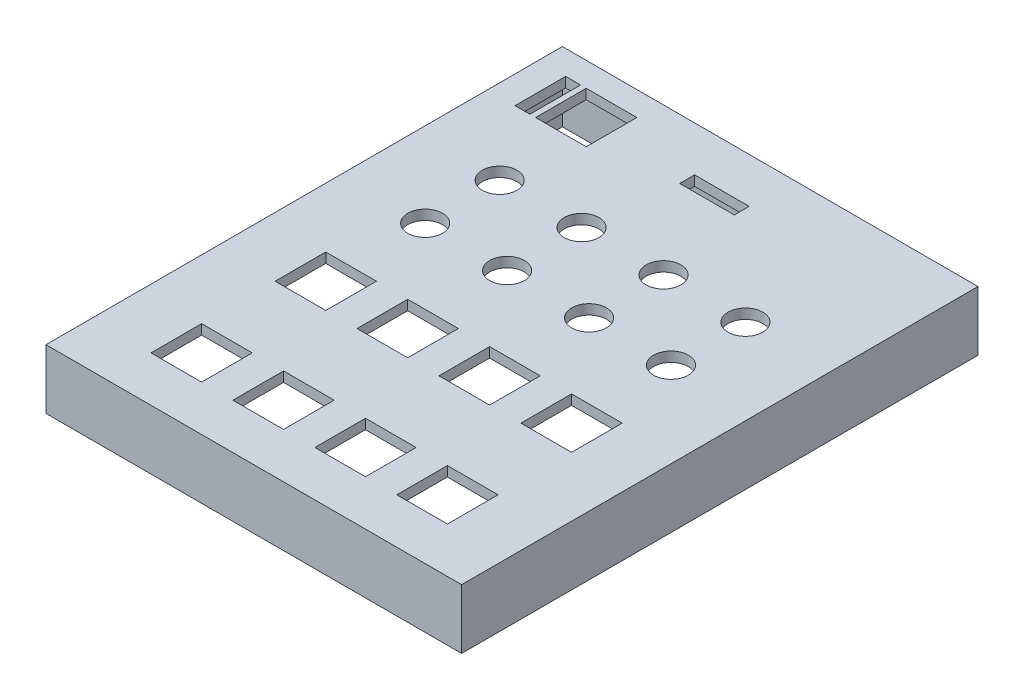
SolidWorks part; units mm, degrees
note: The reader was unsure of these and kept them because the rebuilt part matched: shared geometry of "Sketch1<3>".
ref_plane "Front Plane" through (0, 0, 0) normal (0, 0, 1) x (1, 0, 0)
ref_plane "Top Plane" through (0, 0, 0) normal (0, 1, 0) x (1, 0, 0)
ref_plane "Right Plane" through (0, 0, 0) normal (1, 0, 0) x (0, 0, -1)
sketch "Sketch1" plane through (0, 0, 0) normal (0, 1, 0) x (1, 0, 0)
  line L0 (-91.3497, -4.9786) -> (-81.1497, -4.9786)
  line L1 (-117.8497, 77.6786) -> (-38.1497, 77.6786)
  line L2 (-117.8497, 77.6786) -> (-117.8497, -22.3214)
  line L3 (-117.8497, -22.3214) -> (-38.1497, -22.3214)
  line L4 (-38.1497, 77.6786) -> (-38.1497, -22.3214)
  line L5 (-107.8497, -4.9786) -> (-97.6497, -4.9786)
  line L6 (-107.8497, -4.9786) -> (-107.8497, -15.1786)
  line L7 (-107.8497, -15.1786) -> (-97.6497, -15.1786)
  line L8 (-97.6497, -4.9786) -> (-97.6497, -15.1786)
  line L9 (-81.1497, -4.9786) -> (-81.1497, -15.1786)
  line L10 (-91.3497, -15.1786) -> (-81.1497, -15.1786)
  line L11 (-91.3497, -4.9786) -> (-91.3497, -15.1786)
  line L12 (-74.8497, -4.9786) -> (-64.6497, -4.9786)
  line L13 (-64.6497, -4.9786) -> (-64.6497, -15.1786)
  line L14 (-74.8497, -15.1786) -> (-64.6497, -15.1786)
  line L15 (-74.8497, -4.9786) -> (-74.8497, -15.1786)
  line L16 (-58.3497, -4.9786) -> (-48.1497, -4.9786)
  line L17 (-48.1497, -4.9786) -> (-48.1497, -15.1786)
  line L18 (-58.3497, -15.1786) -> (-48.1497, -15.1786)
  line L19 (-58.3497, -4.9786) -> (-58.3497, -15.1786)
  line L20 (-91.3497, 20.0214) -> (-81.1497, 20.0214)
  line L21 (-107.8497, 20.0214) -> (-97.6497, 20.0214)
  line L22 (-107.8497, 20.0214) -> (-107.8497, 9.8214)
  line L23 (-107.8497, 9.8214) -> (-97.6497, 9.8214)
  line L24 (-97.6497, 20.0214) -> (-97.6497, 9.8214)
  line L25 (-81.1497, 20.0214) -> (-81.1497, 9.8214)
  line L26 (-91.3497, 9.8214) -> (-81.1497, 9.8214)
  line L27 (-91.3497, 20.0214) -> (-91.3497, 9.8214)
  line L28 (-74.8497, 20.0214) -> (-64.6497, 20.0214)
  line L29 (-64.6497, 20.0214) -> (-64.6497, 9.8214)
  line L30 (-74.8497, 9.8214) -> (-64.6497, 9.8214)
  line L31 (-74.8497, 20.0214) -> (-74.8497, 9.8214)
  line L32 (-58.3497, 20.0214) -> (-48.1497, 20.0214)
  line L33 (-48.1497, 20.0214) -> (-48.1497, 9.8214)
  line L34 (-58.3497, 9.8214) -> (-48.1497, 9.8214)
  line L35 (-58.3497, 20.0214) -> (-58.3497, 9.8214)
  line L36 (-119.8497, 79.6786) -> (-119.8497, -24.3214)
  line L37 (-84.1579, 67.6152) -> (-73.1579, 67.6152)
  line L38 (-84.1579, 67.6152) -> (-84.1579, 70.6152)
  line L39 (-84.1579, 70.6152) -> (-73.1579, 70.6152)
  line L40 (-73.1579, 67.6152) -> (-73.1579, 70.6152)
  line L41 (-84.1579, 67.6152) -> (-73.1579, 70.6152) construction
  line L42 (-84.1579, 70.6152) -> (-73.1579, 67.6152) construction
  line L43 (-114.3174, 74.8023) -> (-111.3174, 74.8023)
  line L44 (-114.3174, 74.8023) -> (-114.3174, 64.6023)
  line L45 (-114.3174, 64.6023) -> (-111.3174, 64.6023)
  line L46 (-111.3174, 74.8023) -> (-111.3174, 64.6023)
  line L47 (-114.3174, 74.8023) -> (-111.3174, 64.6023) construction
  line L48 (-114.3174, 64.6023) -> (-111.3174, 74.8023) construction
  line L49 (-110.173, 74.8023) -> (-99.973, 74.8023)
  line L50 (-110.173, 74.8023) -> (-110.173, 64.6023)
  line L51 (-110.173, 64.6023) -> (-99.973, 64.6023)
  line L52 (-99.973, 74.8023) -> (-99.973, 64.6023)
  line L53 (-119.8497, -24.3214) -> (-36.1497, -24.3214)
  line L54 (-36.1497, 79.6786) -> (-36.1497, -24.3214)
  line L55 (-119.8497, 79.6786) -> (-36.1497, 79.6786)
  circle A0 centre (-102.8497, 35.0426) radius 3.5
  circle A1 centre (-86.3497, 35.0426) radius 3.5
  circle A2 centre (-69.8497, 35.0426) radius 3.5
  circle A3 centre (-53.3497, 35.0426) radius 3.5
  circle A4 centre (-102.8497, 50.0426) radius 3.5
  circle A5 centre (-86.3497, 50.0426) radius 3.5
  circle A6 centre (-69.8497, 50.0426) radius 3.5
  circle A7 centre (-53.3497, 50.0426) radius 3.5
  point P38 (-78.6579, 69.1152)
  point P55 (-117.8497, 68.6056)
  point P58 (-112.8174, 69.7023)
  dimension "D5" = 15
  dimension "D1" = 10
  dimension "D3" = 10
  dimension "D8" = 2
  dimension "D2" = 4
  dimension "D4" = 2
  dimension "D6" = 4
  dimension "D7" = 2
extrude "Boss-Extrude1" add sketch "Sketch1" along normal blind 2 contours L4 L1 L2 L3 A7 A6 A5 A4 A3 A2 A1 A0 L40 L37 L38 L39 L35 L32 L33 L34 L31 L28 L29 L30 L27 L20 L25 L26 L19 L16 L17 L18 L15 L12 L13 L14 | A5
extrude "Boss-Extrude2" add sketch "Sketch1<3>" along normal blind 2 and the other way blind 10 contours L55 L36 L53 L54 L1 L4 L3 L2
sketch "Sketch1<3>" plane through (0, 0, 0) normal (0, 1, 0) x (1, 0, 0) same geometry as "Sketch1"
